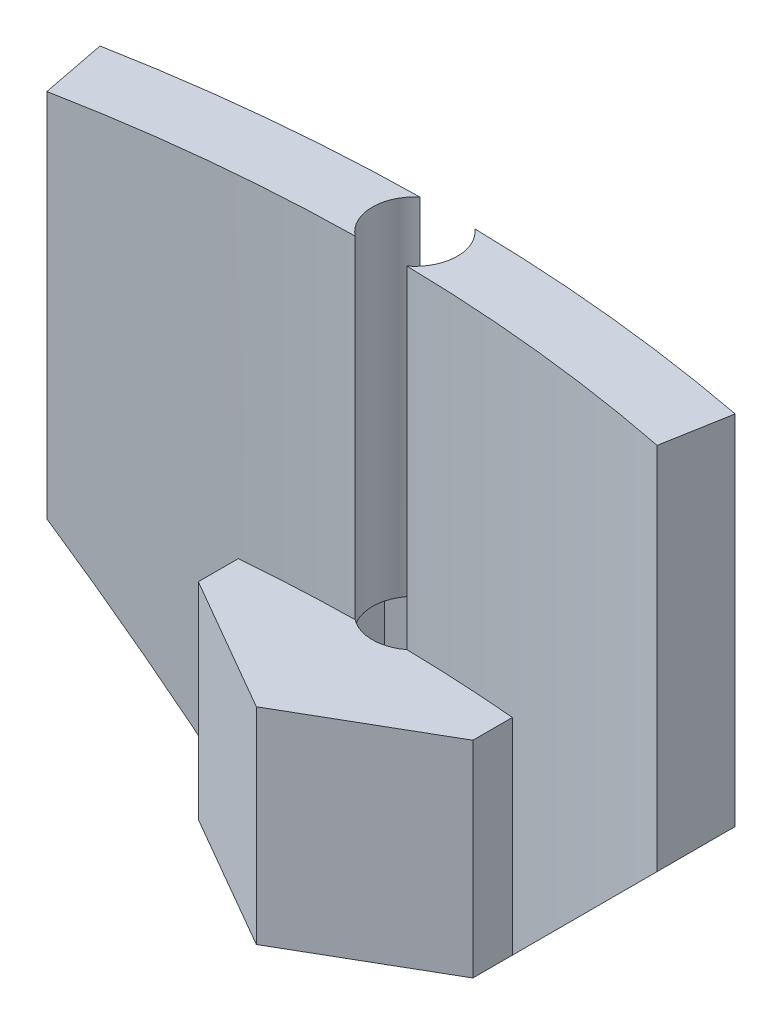
SolidWorks part; units mm, degrees
note: The reader was unsure of these and kept them because the rebuilt part matched: shared geometry of "Sketch1<4>", "Sketch1<5>".
ref_plane "Front Plane" through (0, 0, 0) normal (0, 0, 1) x (1, 0, 0)
ref_plane "Top Plane" through (0, 0, 0) normal (0, 1, 0) x (1, 0, 0)
ref_plane "Right Plane" through (0, 0, 0) normal (1, 0, 0) x (0, 0, -1)
sketch "Sketch1" plane through (0, 0, 0) normal (0, 1, 0) x (1, 0, 0)
  line L0 (-27.0546, 0.7112) -> (-25.1368, -3.9188) construction
  line L1 (26.9996, 0.5784) -> (25.1053, -3.9948) construction
  line L2 (0, 9.3157) -> (0, -7.529) construction
  line L3 (0, 12.8927) -> (-10, 7.1192)
  line L4 (-10, 7.1192) -> (-10, -4.4278)
  line L5 (-10, -4.4278) -> (0, -10.2013)
  line L6 (0, -10.2013) -> (10, -4.4278)
  line L7 (10, -4.4278) -> (10, 7.1192)
  line L8 (10, 7.1192) -> (0, 12.8927)
  line L9 (-26.5907, 0.8978) -> (-24.6773, -3.7216)
  line L10 (26.5376, 0.7697) -> (24.6435, -3.8031)
  line L12 (0, 7.4079) -> (-5.25, 4.3768)
  line L13 (-5.25, 4.3768) -> (-5.25, -1.6854)
  line L14 (-5.25, -1.6854) -> (0, -4.7165)
  line L15 (0, -4.7165) -> (5.25, -1.6854)
  line L16 (5.25, -1.6854) -> (5.25, 4.3768)
  line L17 (5.25, 4.3768) -> (0, 7.4079)
  arc A0 (24.5363, -4.2915) -> (5.1814, -1.725) centre (-0.2034, -116.5989) ccw construction
  arc A1 (-25.1368, -3.9188) -> (-24.5775, -4.2116) centre (-24.6819, -3.7304) ccw construction
  arc A2 (-27.0546, 0.7112) -> (-26.7017, 1.3853) centre (-26.5966, 0.9009) cw construction
  arc A3 (-26.7017, 1.3853) -> (-5.25, 4.1244) centre (-0.2034, -120.7737) cw construction
  arc A4 (26.615, 1.3155) -> (26.9996, 0.5784) centre (26.4986, 0.7859) cw construction
  arc A5 (25.1053, -3.9948) -> (24.5363, -4.2915) centre (24.6438, -3.8037) cw construction
  circle A6 centre (0, 1.3457) radius 10 construction
  arc A7 (-24.6773, -3.7216) -> (-24.6773, -3.7216) centre (-24.6773, -3.7216) ccw
  arc A8 (24.6435, -3.8031) -> (5.25, -1.2277) centre (-0.2034, -116.5989) ccw
  arc A9 (24.6435, -3.8031) -> (24.6435, -3.8031) centre (24.6435, -3.8031) cw
  arc A10 (26.5077, 0.8271) -> (26.5376, 0.7697) centre (26.4986, 0.7859) cw
  arc A11 (-26.5907, 0.8978) -> (-5.25, 3.6239) centre (-0.2034, -120.7737) cw
  arc A12 (-26.5907, 0.8978) -> (-26.5907, 0.8978) centre (-26.5907, 0.8978) cw
  circle A13 centre (0, 1.3457) radius 5.25 construction
  arc A14 (-4.72, 3.6443) -> (0, 3.7261) centre (-0.2034, -120.7737) cw
  arc A15 (5.25, 3.6068) -> (26.5077, 0.8271) centre (-0.2034, -120.7737) cw
  arc A16 (-26.5907, 0.8978) -> (26.5077, 0.8271) centre (-0.2034, -120.7737) cw construction
  arc A17 (-4.4354, 4.1546) -> (0, 4.2261) centre (-0.2034, -120.7737) cw construction
  arc A18 (5.25, 4.1073) -> (26.615, 1.3155) centre (-0.2034, -120.7737) cw construction
  arc A19 (-26.7017, 1.3853) -> (26.615, 1.3155) centre (-0.2034, -120.7737) cw construction
  arc A20 (0, 3.7261) -> (4.7277, 3.6286) centre (-0.2034, -120.7737) cw
  arc A21 (0, 4.2261) -> (4.4447, 4.1398) centre (-0.2034, -120.7737) cw construction
  arc A22 (4.5924, -1.1985) -> (0, -1.0991) centre (-0.2034, -116.5989) ccw
  arc A23 (-5.25, -1.2092) -> (-24.6773, -3.7216) centre (-0.2034, -116.5989) ccw
  arc A24 (24.6435, -3.8031) -> (-24.6773, -3.7216) centre (-0.2034, -116.5989) ccw construction
  arc A25 (4.2858, -1.6865) -> (0, -1.5991) centre (-0.2034, -116.5989) ccw construction
  arc A26 (-5.2109, -1.708) -> (-24.5775, -4.2116) centre (-0.2034, -116.5989) ccw construction
  arc A27 (24.5363, -4.2915) -> (-24.5775, -4.2116) centre (-0.2034, -116.5989) ccw construction
  arc A28 (0, -1.0991) -> (-4.6011, -1.1826) centre (-0.2034, -116.5989) ccw
  arc A29 (0, -1.5991) -> (-4.2962, -1.6717) centre (-0.2034, -116.5989) ccw construction
  arc A30 (-4.6011, -1.1826) -> (-5.25, -1.2092) centre (-0.2034, -116.5989) ccw
  arc A31 (-4.2962, -1.6717) -> (-5.2109, -1.708) centre (-0.2034, -116.5989) ccw construction
  arc A32 (-5.25, 4.1244) -> (-4.4354, 4.1546) centre (-0.2034, -120.7737) cw construction
  arc A33 (-5.25, 3.6239) -> (-4.72, 3.6443) centre (-0.2034, -120.7737) cw
  arc A34 (4.4447, 4.1398) -> (5.25, 4.1073) centre (-0.2034, -120.7737) cw construction
  arc A35 (4.7277, 3.6286) -> (5.25, 3.6068) centre (-0.2034, -120.7737) cw
  arc A36 (5.1814, -1.725) -> (4.2858, -1.6865) centre (-0.2034, -116.5989) ccw construction
  arc A37 (5.25, -1.2277) -> (4.5924, -1.1985) centre (-0.2034, -116.5989) ccw
  dimension "D1" = 115
  dimension "D2" = 125
  dimension "D3" = 45
  dimension "D4" = 4.1749
  dimension "D5" = 116.5989
  dimension "D6" = 49.3256
  dimension "D7" = 53.0952
  dimension "D8" = 0.7859
  dimension "D9" = 4.5895
  dimension "D11" = 20
  dimension "D12" = 10.5
  dimension "D10" = 0.5
extrude "Boss-Extrude1" add sketch "Sketch1" along normal blind 7 contours A23 L4 A11 L9 | A23 L13 A11 L4 | A15 L16 A8 L7 | A15 L7 A8 L10 A10
extrude "Boss-Extrude3" add sketch "Sketch1<4>" against normal blind 15 contours L8 L3 L4 L5 L6 L7 | L17 L12 L13 L14 L15 L16
sketch "Sketch1<4>" plane through (0, 0, 0) normal (0, 1, 0) x (1, 0, 0) same geometry as "Sketch1"
extrude "Boss-Extrude4" add sketch "Sketch1<5>" against normal blind 1 contours L3 L4 L5 L6 L7 L8
sketch "Sketch1<5>" plane through (0, 0, 0) normal (0, 1, 0) x (1, 0, 0) same geometry as "Sketch1"
sketch "Sketch2" plane through (0, -1, 0) normal (0, -1, 0) x (1, 0, 0)
  line L0 (-5.25, 1.6854) -> (-5.25, -4.3768) construction
  circle A0 centre (0, -1.3457) radius 3.1
  point P5 (-5.25, -1.3457)
  dimension "D1" = 6.2
extrude "Cut-Extrude1" cut sketch "Sketch2" against normal through all both and the other way through all
sketch "Sketch3" plane through (0, 7, 0) normal (0, 1, 0) x (1, 0, 0)
  line L0 (-26.5907, 0.8978) -> (-24.6773, -3.7216) construction
  line L1 (24.6435, -3.8031) -> (26.5376, 0.7697) construction
  line L2 (-26.5907, 0.8978) -> (-24.6773, -3.7216) construction
  line L3 (24.6435, -3.8031) -> (26.5376, 0.7697) construction
  line L4 (-23.1766, 1.5883) -> (-22.2418, -3.2209)
  line L5 (0, 0) -> (0, 15.8879) construction
  line L6 (23.1766, 1.5883) -> (22.3121, -3.3147)
  arc A0 (-2.0011, 3.7133) -> (-1.8904, -1.1112) centre (0, 1.3457) ccw construction
  arc A1 (-2.0011, 3.7133) -> (-26.5907, 0.8978) centre (-0.2034, -120.7737) ccw construction
  arc A2 (-1.8904, -1.1112) -> (-24.6773, -3.7216) centre (-0.2034, -116.5989) ccw construction
  arc A3 (1.8819, -1.1177) -> (2.009, 3.7066) centre (0, 1.3457) ccw construction
  arc A4 (24.6435, -3.8031) -> (1.8819, -1.1177) centre (-0.2034, -116.5989) ccw construction
  arc A5 (26.5376, 0.7697) -> (26.5077, 0.8271) centre (26.4986, 0.7859) ccw construction
  arc A6 (26.5077, 0.8271) -> (2.009, 3.7066) centre (-0.2034, -120.7737) ccw construction
  arc A7 (-2.0011, 3.7133) -> (-1.8904, -1.1112) centre (0, 1.3457) ccw
  arc A8 (-2.0011, 3.7133) -> (-23.1766, 1.5883) centre (-0.2034, -120.7737) ccw
  arc A9 (-1.8904, -1.1112) -> (-22.2418, -3.2209) centre (-0.2034, -116.5989) ccw
  arc A10 (1.8819, -1.1177) -> (2.009, 3.7066) centre (0, 1.3457) ccw
  arc A11 (24.6435, -3.8031) -> (1.8819, -1.1177) centre (-0.2034, -116.5989) ccw
  arc A12 (26.5376, 0.7697) -> (26.5077, 0.8271) centre (26.4986, 0.7859) ccw
  arc A13 (21.0963, 1.8908) -> (2.009, 3.7066) centre (-0.2034, -120.7737) ccw
  arc A14 (-2.0011, 3.7133) -> (-26.5907, 0.8978) centre (-0.2034, -120.7737) ccw construction
  arc A15 (-23.1766, 1.5883) -> (-26.5907, 0.8978) centre (-0.2034, -120.7737) ccw construction
  arc A16 (-22.2418, -3.2209) -> (-24.6773, -3.7216) centre (-0.2034, -116.5989) ccw construction
  arc A17 (26.5077, 0.8271) -> (21.0963, 1.8908) centre (-0.2034, -120.7737) ccw construction
  arc A18 (24.6435, -3.8031) -> (1.8819, -1.1177) centre (-0.2034, -116.5989) ccw construction
  arc M5 (2.009, 3.7066) -> (1.8819, -1.1177) centre (0, 1.3457) cw
  arc M6 (1.8819, -1.1177) -> (24.6435, -3.8031) centre (-0.2034, -116.5989) cw
  arc M9 (26.5077, 0.8271) -> (2.009, 3.7066) centre (-0.2034, -120.7737) ccw
  dimension "D1" = 11
  dimension "D2" = 10
  dimension "D3" = 22.2418
extrude "Boss-Extrude5" add sketch "Sketch3" along normal blind 17.2 contours A9 A7 A8 L4 | L6 M9 M5 M6
sketch "Sketch4" plane through (0, 7, 0) normal (0, 1, 0) x (1, 0, 0)
  line L0 (0, 0) -> (0, 18.7025) construction
  line L2 (23.1635, 1.5138) -> (22.3121, -3.3147)
  line L3 (24.6435, -3.8031) -> (26.5376, 0.7697)
  line L4 (23.1635, 1.5138) -> (22.3121, -3.3147)
  line L5 (24.6435, -3.8031) -> (26.5376, 0.7697)
  line L7 (-22.2418, -3.2209) -> (-23.1766, 1.5883)
  line L8 (-26.5907, 0.8978) -> (-24.6773, -3.7216)
  line L9 (-22.2418, -3.2209) -> (-23.1766, 1.5883)
  line L10 (-26.5907, 0.8978) -> (-24.6773, -3.7216)
  arc A2 (-22.2418, -3.2209) -> (-24.6773, -3.7216) centre (-0.2034, -116.5989) ccw
  arc A3 (24.6435, -3.8031) -> (22.3121, -3.3147) centre (-0.2034, -116.5989) ccw
  arc A4 (26.5376, 0.7697) -> (26.5077, 0.8271) centre (26.4986, 0.7859) ccw
  arc A5 (26.5077, 0.8271) -> (23.1635, 1.5138) centre (-0.2034, -120.7737) ccw
  arc A6 (24.6435, -3.8031) -> (22.3121, -3.3147) centre (-0.2034, -116.5989) ccw
  arc A7 (26.5376, 0.7697) -> (26.5077, 0.8271) centre (26.4986, 0.7859) ccw
  arc A8 (26.5077, 0.8271) -> (23.1635, 1.5138) centre (-0.2034, -120.7737) ccw
  arc A9 (-23.1766, 1.5883) -> (-26.5907, 0.8978) centre (-0.2034, -120.7737) ccw
  arc A10 (-22.2418, -3.2209) -> (-24.6773, -3.7216) centre (-0.2034, -116.5989) ccw
  arc A11 (-23.1766, 1.5883) -> (-26.5907, 0.8978) centre (-0.2034, -120.7737) ccw
  dimension "D2" = 0
  dimension "D1" = 0
extrude "Cut-Extrude3" cut sketch "Sketch4" against normal through all both and the other way through all
chamfer "Chamfer1" distance 15 angle 45 2 edges at (10, 0, -0.8785) (-10, 0, -0.9126)
